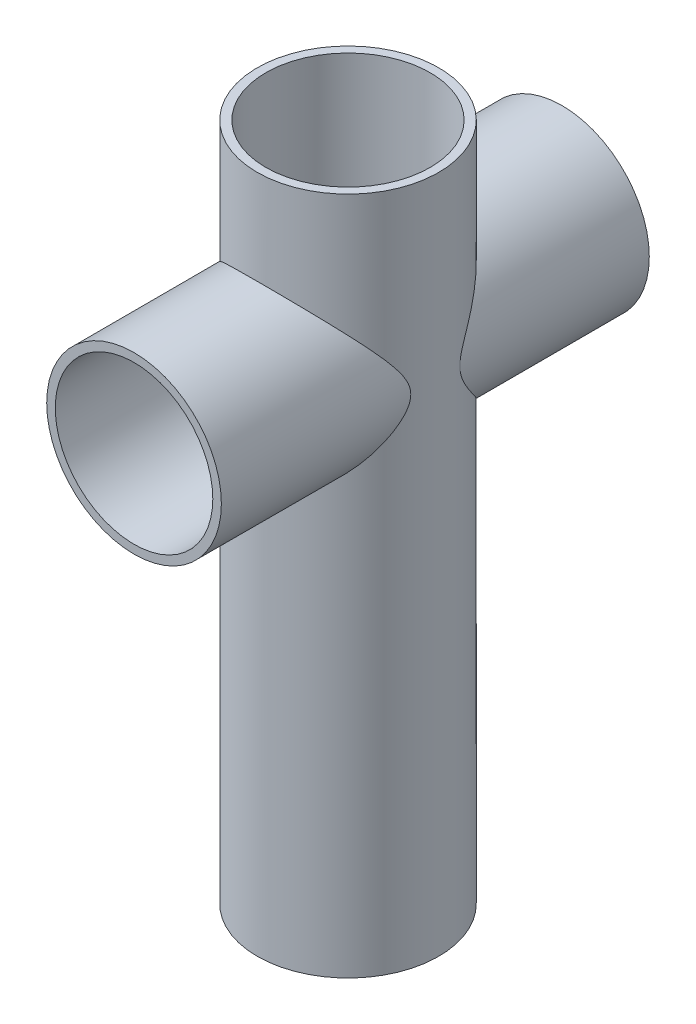
SolidWorks part; units mm, degrees
ref_plane "Front" through (0, 0, 0) normal (0, 0, 1) x (1, 0, 0)
ref_plane "Top" through (0, 0, 0) normal (0, 1, 0) x (1, 0, 0)
ref_plane "Right" through (0, 0, 0) normal (1, 0, 0) x (0, 0, -1)
ref_plane "Plane1" through (0, 0, -1) normal (0, 0, 1) x (1, 0, 0)
ref_plane "Plane2" through (0, 0, 10) normal (0, 0, 1) x (1, 0, 0)
sketch "Sketch2" plane through (0, 0, -1) normal (0, 0, 1) x (1, 0, 0)
  line L0 (-159.4387, 154.3507) -> (137.2047, 154.3507) construction
  line L1 (-252.9462, -150.4188) -> (39.1606, -71.0441) construction
sketch "Sketch6" plane through (0, 0, 0) normal (0, 0, 1) x (1, 0, 0)
  line L0 (0, 0) -> (0, 27.8802) construction
  line L1 (-21.1979, 0) -> (21.1979, 0)
  line L2 (-21.1979, 0) -> (-21.1979, 180.6476)
  line L3 (-21.1979, 180.6476) -> (21.1979, 180.6476)
  line L4 (21.1979, 0) -> (21.1979, 180.6476)
  line L5 (-47.3805, 180.6476) -> (47.3805, 180.6476)
  line L6 (-47.3805, 180.6476) -> (-47.3805, 185.0788)
  line L7 (-47.3805, 185.0788) -> (47.3805, 185.0788)
  line L8 (47.3805, 180.6476) -> (47.3805, 185.0788)
  line L9 (-47.3805, 180.6476) -> (47.3805, 185.0788) construction
  line L10 (-47.3805, 185.0788) -> (47.3805, 180.6476) construction
  line L12 (-24.2143, 185.0788) -> (24.2143, 185.0788)
  line L13 (-24.2143, 185.0788) -> (-24.2143, 216.3885)
  line L14 (-24.2143, 216.3885) -> (24.2143, 216.3885)
  line L15 (24.2143, 185.0788) -> (24.2143, 216.3885)
  line L16 (-24.2143, 185.0788) -> (24.2143, 216.3885) construction
  line L17 (-24.2143, 216.3885) -> (24.2143, 185.0788) construction
  line L18 (-25.9834, 216.3885) -> (25.9834, 216.3885)
  line L19 (-25.9834, 216.3885) -> (-25.9834, 235.7838)
  line L20 (-25.9834, 235.7838) -> (25.9834, 235.7838)
  line L21 (25.9834, 216.3885) -> (25.9834, 235.7838)
  line L22 (-25.9834, 216.3885) -> (25.9834, 235.7838) construction
  line L23 (-25.9834, 235.7838) -> (25.9834, 216.3885) construction
  point P4 (0, 182.8632)
  point P11 (0, 200.7337)
  point P16 (0, 226.0862)
  dimension "D1" = 42.3958
  dimension "D2" = 180.6476
  dimension "D3" = 31.3098
  dimension "D4" = 51.9668
  dimension "D5" = 94.7609
  dimension "D6" = 48.4286
  dimension "D7" = 19.3952
  dimension "D8" = 4.4312
sketch "Sketch7" plane through (0, 0, 0) normal (0, 1, 0) x (1, 0, 0)
  circle A0 centre (0, 0) radius 21.1979
extrude "Boss-Extrude1" add sketch "Sketch7" along normal up to vertex (180.6476 mm away) up to point (-21.1979, 180.6476, 0)
sketch "Sketch12" plane through (0, 0, 0) normal (0, 0, 1) x (1, 0, 0)
  circle A0 centre (0, 116.1951) radius 20.407
extrude "Boss-Extrude6" add sketch "Sketch12" against normal mid plane 100
shell "Shell1" thickness 2 removed face at (20.407, 116.1951, -50) removed face at (20.407, 116.1951, 50) removed face at (0, 0, 21.1979)
sketch "Sketch13" plane through (0, 180.6476, 0) normal (0, 1, 0) x (1, 0, 0)
  circle A0 centre (0, 0) radius 21.1979
extrude "Cut-Extrude1" cut sketch "Sketch13" against normal blind 22
